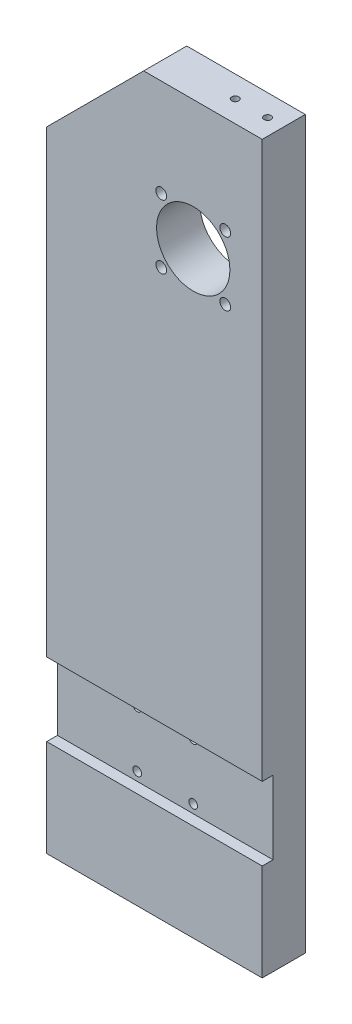
SolidWorks part; units mm, degrees
ref_plane "Front Plane" through (0, 0, 0) normal (0, 0, 1) x (1, 0, 0)
ref_plane "Top Plane" through (0, 0, 0) normal (0, 1, 0) x (1, 0, 0)
ref_plane "Right Plane" through (0, 0, 0) normal (1, 0, 0) x (0, 0, -1)
sketch "Sketch1" plane through (0, 0, 0) normal (0, 0, 1) x (1, 0, 0)
  line L0 (65.7045, 560.5004) -> (50.8553, 575.3496) construction
  line L1 (65.7045, 560.5004) -> (44.7045, 560.5004) construction
  line L2 (65.7045, 560.5004) -> (65.7045, 581.5004) construction
  line L3 (47.7045, 545.8558) -> (47.7045, 439.2537) construction
  line L4 (7.7288, 345.5004) -> (63.5732, 345.5004) construction
  line L5 (97.7045, 283.5004) -> (-2.2955, 283.5004)
  line L6 (97.7045, 283.5004) -> (97.7045, 620.5004)
  line L7 (97.7045, 620.5004) -> (-2.2955, 620.5004)
  line L8 (-2.2955, 283.5004) -> (-2.2955, 620.5004)
  line L9 (97.7045, 283.5004) -> (-2.2955, 620.5004) construction
  line L10 (97.7045, 620.5004) -> (-2.2955, 283.5004) construction
  circle A0 centre (65.7045, 560.5004) radius 17
  circle A1 centre (65.7045, 560.5004) radius 21 construction
  circle A2 centre (80.5538, 575.3496) radius 2.5
  circle A3 centre (80.5538, 545.6511) radius 2.5
  circle A4 centre (50.8553, 545.6511) radius 2.5
  circle A5 centre (50.8553, 575.3496) radius 2.5
  circle A6 centre (34.7045, 358.5004) radius 2
  circle A7 centre (60.7045, 358.5004) radius 2
  circle A8 centre (60.7045, 332.5004) radius 2
  circle A9 centre (34.7045, 332.5004) radius 2
  point P5 (50.8553, 575.3496)
  point P6 (80.5538, 575.3496)
  point P7 (80.5538, 545.6511)
  point P8 (50.8553, 545.6511)
  point P19 (47.7045, 452.0004)
  dimension "D2" = 5
  dimension "D3" = 34
  dimension "D4" = 42
  dimension "D10" = 4
  dimension "D1" = 45
  dimension "D5" = 337
  dimension "D6" = 100
  dimension "D7" = 60
  dimension "D8" = 13
  dimension "D9" = 13
  dimension "D11" = 62
  dimension "D12" = 32
extrude "Boss-Extrude1" add sketch "Sketch1" along normal blind 20
chamfer "Chamfer1" distance 45 angle 45 1 edges at (-2.2955, 620.5004, 10)
sketch "Sketch2" plane through (0, 0, 20) normal (0, 0, 1) x (1, 0, 0)
  line L0 (60.7045, 358.5004) -> (34.7045, 332.5004) construction
  line L1 (34.7045, 358.5004) -> (60.7045, 332.5004) construction
  line L3 (97.7045, 328.5004) -> (-2.2955, 328.5004)
  line L4 (97.7045, 328.5004) -> (97.7045, 362.5004)
  line L5 (97.7045, 362.5004) -> (-2.2955, 362.5004)
  line L6 (-2.2955, 328.5004) -> (-2.2955, 362.5004)
  line L7 (97.7045, 328.5004) -> (-2.2955, 362.5004) construction
  line L8 (97.7045, 362.5004) -> (-2.2955, 328.5004) construction
  point P8 (47.7045, 345.5004)
  point P9 (47.7045, 345.5004)
  dimension "D1" = 100
  dimension "D2" = 34
extrude "Cut-Extrude1" cut sketch "Sketch2" against normal blind 5
sketch "Sketch3" plane through (0, 283.5004, 0) normal (0, -1, 0) x (1, 0, 0)
  line L0 (-2.2955, 10) -> (97.7045, 10) construction
  line L1 (-2.2955, 20) -> (-2.2955, 0) construction
  line L2 (97.7045, 20) -> (97.7045, 0) construction
  line L3 (47.7045, 20) -> (47.7045, 0) construction
  line L4 (-2.2955, 20) -> (97.7045, 20) construction
  line L5 (-2.2955, 0) -> (97.7045, 0) construction
  point P12 (67.7045, 10)
  point P13 (87.7045, 10)
  point P14 (7.7045, 10)
  point P15 (27.7045, 10)
  dimension "D1" = 20
  dimension "D2" = 40
hole_wizard "M4 Tapped Hole1" positions "3DSketch1" profile "Sketch4" tap size "M4" standard "ISO"
sketch3d "3DSketch1"
  point P0 (7.7045, 283.5004, 10)
  point P10 (27.7045, 283.5004, 10)
  point P13 (67.7045, 283.5004, 10)
  point P16 (87.7045, 283.5004, 10)
sketch "Sketch4" plane through (7.7045, 283.5004, 10) normal (1, 0, 0) x (0, 0, -1)
  line L0 (0, 0) -> (0, 17.0914)
  line L1 (0, 17.0914) -> (1.65, 16.1)
  line L2 (1.65, 16.1) -> (1.65, 0)
  line L5 (1.65, 0) -> (0, 0)
  line L10 (0, 17.0914) -> (-1.65, 16.1) construction
  line L11 (0, -6.35) -> (0, 107.95) construction
  dimension "Tap Drill Dia." = 3.3
  dimension "Tap Drill Depth" = 16.1
  dimension "Drill Angle" = 118
sketch "Sketch5" plane through (0, 620.5004, 0) normal (0, 1, 0) x (1, 0, 0)
  point P0 (90.2045, -10)
  point P1 (75.2045, -10)
hole_wizard "M4 Tapped Hole2" positions "3DSketch2" profile "Sketch6" tap size "M4" standard "ISO"
sketch3d "3DSketch2"
  line L0 (90.2045, 625.5004, 10) -> (90.2045, 620.5004, 10) construction
  line L1 (75.2045, 625.5004, 10) -> (75.2045, 620.5004, 10) construction
  point P0 (90.2045, 625.5004, 10)
  point P4 (75.2045, 625.5004, 10)
sketch "Sketch6" plane through (90.2045, 625.5004, 10) normal (1, 0, 0) x (0, 0, 1)
  line L0 (0, 0) -> (0, 16.0914)
  line L1 (0, 16.0914) -> (1.65, 15.1)
  line L2 (1.65, 15.1) -> (1.65, 0)
  line L5 (1.65, 0) -> (0, 0)
  line L10 (0, 16.0914) -> (-1.65, 15.1) construction
  line L11 (0, -6.35) -> (0, 107.95) construction
  dimension "Tap Drill Dia." = 3.3
  dimension "Tap Drill Depth" = 15.1
  dimension "Drill Angle" = 118
